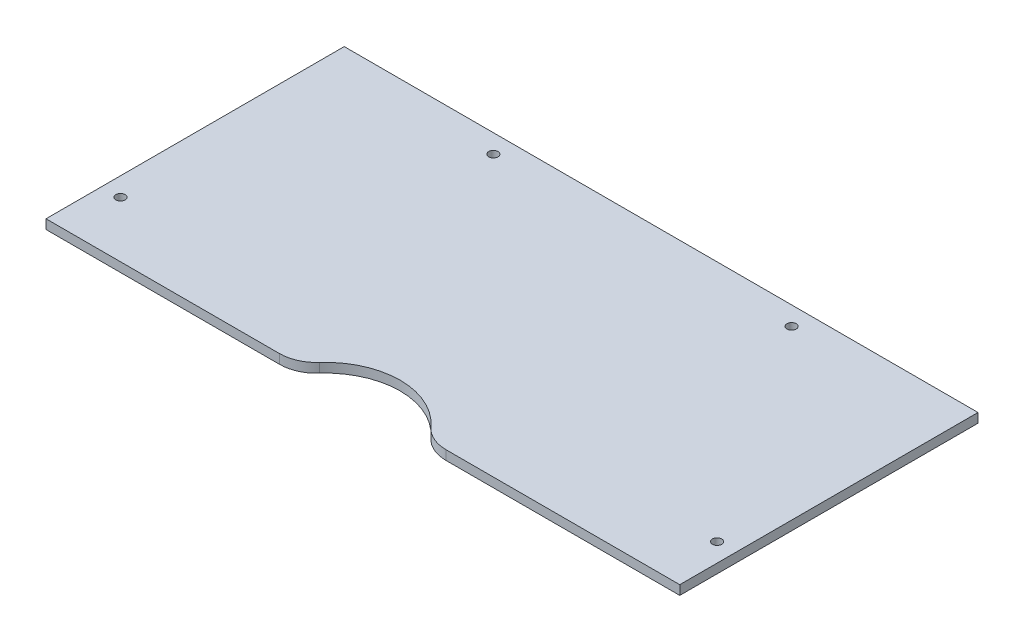
SolidWorks part; units mm, degrees
material "Zoltek Panex 33"
ref_plane "Front Plane" through (0, 0, 0) normal (0, 0, 1) x (1, 0, 0)
ref_plane "Top Plane" through (0, 0, 0) normal (0, 1, 0) x (1, 0, 0)
ref_plane "Right Plane" through (0, 0, 0) normal (1, 0, 0) x (0, 0, -1)
sketch "Sketch1" plane through (0, 0, 0) normal (0, 1, 0) x (1, 0, 0)
  line L0 (0, 101.6) -> (0, 0)
  line L1 (0, 0) -> (215.9, 0)
  line L2 (0, 0) -> (0, 228.6)
  line L3 (0, 228.6) -> (215.9, 228.6)
  line L4 (215.9, 0) -> (215.9, 228.6)
  line L5 (0, 127) -> (85.953, 127)
  line L6 (0, 127) -> (0, 101.6)
  line L7 (0, 101.6) -> (85.953, 101.6)
  line L8 (85.953, 127) -> (85.953, 101.6)
  line L9 (215.9, 127) -> (129.947, 127)
  line L10 (215.9, 127) -> (215.9, 101.6)
  line L11 (215.9, 101.6) -> (129.947, 101.6)
  line L12 (129.947, 127) -> (129.947, 101.6)
  line L13 (215.9, 0) -> (215.9, 101.6)
  circle A0 centre (107.95, 114.3) radius 25.4
  point P13 (85.953, 114.3)
  point P18 (0, 114.3)
  dimension "D4" = 50.8
  dimension "D5" = 85.953
  dimension "D1" = 228.6
  dimension "D2" = 215.9
  dimension "D3" = 25.4
extrude "Boss-Extrude1" add sketch "Sketch1" along normal blind 3.175 contours A0 L9 L4 L3 L2 L5 region at (107.95, 0, -178.6387)
fillet "Fillet1" radius 12.7 2 edges at (129.947, 1.5875, -127) (85.953, 1.5875, -127)
sketch "Sketch2" plane through (0, 3.175, 0) normal (0, 1, 0) x (1, 0, 0)
  line L0 (0, 127) -> (0, 228.6) construction
  line L1 (0, 228.6) -> (215.9, 228.6) construction
  line L2 (215.9, 127) -> (215.9, 228.6) construction
  line L3 (0, 127) -> (79.5519, 127) construction
  line L4 (215.9, 127) -> (136.3481, 127) construction
  circle A0 centre (6.35, 146.05) radius 1.5875
  circle A1 centre (57.15, 222.25) radius 1.5875
  circle A2 centre (158.75, 222.25) radius 1.5875
  circle A3 centre (209.55, 146.05) radius 1.5875
  dimension "D1" = 3.175
  dimension "D2" = 6.35
  dimension "D3" = 6.35
  dimension "D4" = 6.35
  dimension "D5" = 6.35
  dimension "D6" = 57.15
  dimension "D7" = 19.05
  dimension "D8" = 57.15
  dimension "D9" = 19.05
extrude "Cut-Extrude1" cut sketch "Sketch2" against normal through all
